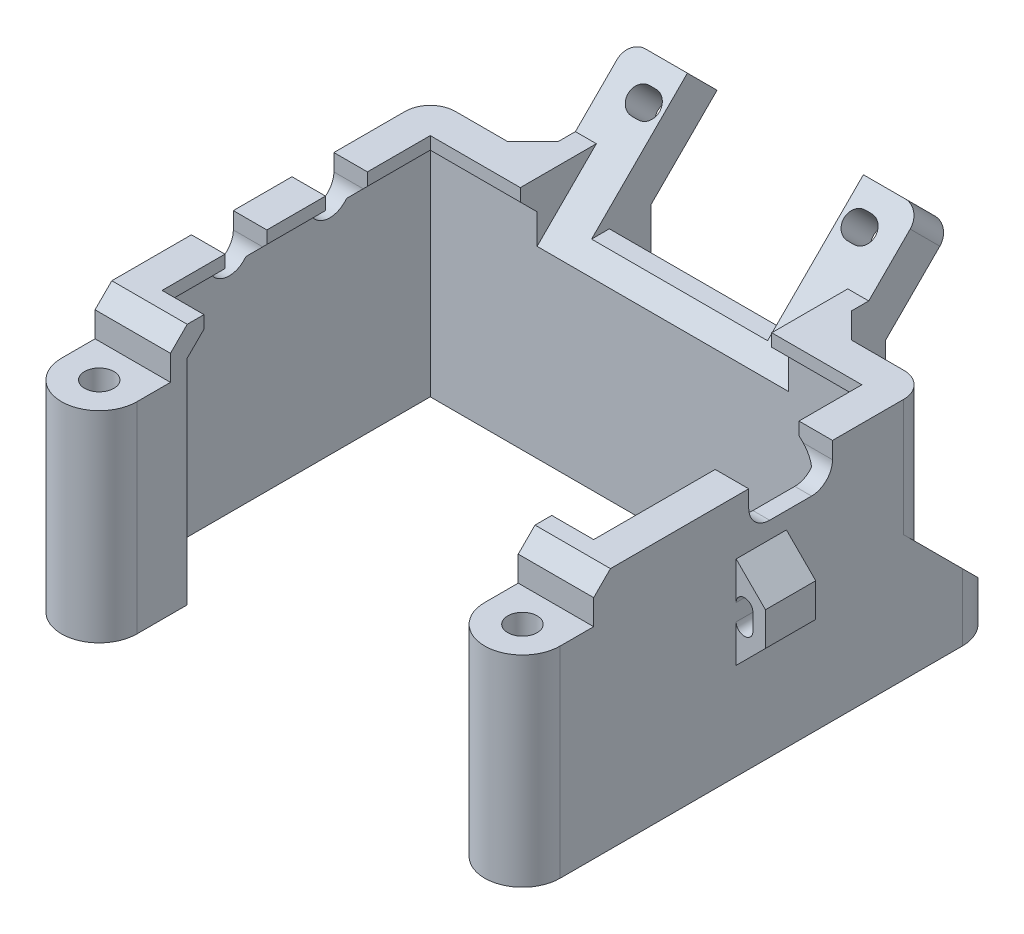
SolidWorks part; units mm, degrees
ref_plane "Front Plane" through (0, 0, 0) normal (0, 0, 1) x (1, 0, 0)
ref_plane "Top Plane" through (0, 0, 0) normal (0, 1, 0) x (1, 0, 0)
ref_plane "Right Plane" through (0, 0, 0) normal (1, 0, 0) x (0, 0, -1)
sketch "Sketch1" plane through (0, 0, 0) normal (0, 1, 0) x (1, 0, 0)
  line L0 (-29.75, 20) -> (29.75, 20)
  line L1 (-27.75, -18) -> (-20.75, -18)
  line L2 (-27.75, -18) -> (-27.75, 18)
  line L3 (-27.75, 18) -> (27.75, 18)
  line L4 (27.75, -18) -> (27.75, 18)
  line L5 (-27.75, -18) -> (27.75, 18) construction
  line L6 (-27.75, 18) -> (27.75, -18) construction
  line L7 (29.75, -20) -> (29.75, 20)
  line L8 (-29.75, -20) -> (-20.75, -20)
  line L9 (-29.75, -20) -> (-29.75, 20)
  line L10 (-20.75, -18) -> (-20.75, -20)
  line L11 (20.75, -18) -> (20.75, -20)
  line L12 (20.75, -18) -> (27.75, -18)
  line L13 (-27.75, -18) -> (27.75, -18) construction
  line L14 (20.75, -20) -> (29.75, -20)
  line L15 (-29.75, -20) -> (29.75, -20) construction
  point P0 (0, 0)
  dimension "D1" = 55.5
  dimension "D2" = 36
  dimension "D4" = 9
  dimension "D3" = 2
extrude "Boss-Extrude1" add sketch "Sketch1" along normal blind 29
sketch "Sketch2" plane through (0, 0, 0) normal (1, 0, 0) x (0, 0, -1)
  line L0 (18, 0) -> (18, 21.9289)
  line L1 (18, 21.9289) -> (31.435, 35.364)
  line L2 (31.435, 35.364) -> (34.9706, 31.8284)
  line L3 (34.9706, 31.8284) -> (23, 19.8579)
  line L4 (18, 0) -> (23, 0)
  line L5 (23, 0) -> (23, 19.8579)
  dimension "D1" = 45
  dimension "D2" = 5
  dimension "D3" = 5
  dimension "D4" = 19
  dimension "D5" = 5
extrude "Boss-Extrude2" add sketch "Sketch2" against normal blind 7 from offset 10.5 offset against normal yes
mirror "Mirror1" about plane through (0, 0, 0) normal (1, 0, 0) of "Boss-Extrude2"
sketch "Sketch3" plane through (0, 0, 0) normal (1, 0, 0) x (0, 0, -1)
  line L0 (18, 21.9289) -> (18, 29)
  line L1 (18, 29) -> (25.0711, 29)
  line L2 (25.0711, 29) -> (18, 21.9289)
  line L3 (18, 29) -> (18, 0) construction
  line L4 (20, 29) -> (-20, 29) construction
  line L5 (31.435, 35.364) -> (20, 23.9289) construction
extrude "Cut-Extrude1" cut sketch "Sketch3" against normal mid plane 30
sketch "Sketch4" plane through (0, 1.9645, 1.9645) normal (0, 0.7071, 0.7071) x (1, 0, 0)
  line L0 (-12.5, 43.234) -> (12.5, 43.234) construction
  line L1 (0, 43.234) -> (0, 0) construction
  line L2 (-15, 28.234) -> (15, 28.234) construction
  line L3 (-12.5, 43.234) -> (-13.25, 43.234) construction
  line L4 (-12.5, 41.734) -> (-13.25, 41.734)
  line L5 (-12.5, 44.734) -> (-13.25, 44.734)
  line L6 (12.5, 43.234) -> (13.25, 43.234) construction
  line L7 (12.5, 44.734) -> (13.25, 44.734)
  line L8 (12.5, 41.734) -> (13.25, 41.734)
  arc A0 (-12.5, 41.734) -> (-12.5, 44.734) centre (-12.5, 43.234) ccw
  arc A1 (-13.25, 44.734) -> (-13.25, 41.734) centre (-13.25, 43.234) ccw
  arc A2 (12.5, 44.734) -> (12.5, 41.734) centre (12.5, 43.234) ccw
  arc A3 (13.25, 41.734) -> (13.25, 44.734) centre (13.25, 43.234) ccw
  point P2 (-12.875, 43.234)
  point P13 (12.875, 43.234)
  dimension "D2" = 3
  dimension "D1" = 15
  dimension "D3" = 25
  dimension "D4" = 0.75
extrude "Cut-Extrude2" cut sketch "Sketch4" against normal up to next
sketch "Sketch7" plane through (-17.5, 0, 0) normal (-1, 0, 0) x (0, 0, 1)
  line L0 (-25.0711, 29) -> (-20, 29)
  line L1 (-31.435, 35.364) -> (-20, 23.9289) construction
  line L2 (-20, 29) -> (-20, 23.9289)
  line L3 (-20, 23.9289) -> (-25.0711, 29)
extrude "Boss-Extrude4" add sketch "Sketch7" against normal blind 2.5
mirror "Mirror2" about plane through (0, 0, 0) normal (1, 0, 0) of "Boss-Extrude4"
sketch "Sketch6" plane through (0, 0, -20) normal (0, 0, -1) x (-1, 0, 0)
  line L4 (10.5, 0) -> (10.5, 23.9289)
  line L5 (10.5, 23.9289) -> (-10.5, 23.9289)
  line L6 (-10.5, 23.9289) -> (-10.5, 0)
  line L7 (-10.5, 0) -> (10.5, 0)
  line L8 (10.5, 0) -> (10.5, 23.9289)
  line L9 (10.5, 23.9289) -> (-10.5, 23.9289)
  line L10 (-10.5, 23.9289) -> (-10.5, 0)
  line L11 (-10.5, 0) -> (10.5, 0)
  dimension "D1" = 0
extrude "Boss-Extrude3" add sketch "Sketch6" along normal up to surface (3 mm away) up to face at (14, 9.9289, -23)
chamfer "Chamfer1" distance 3 angle 45 2 edges at (-17.5, 14.5, -20) (17.5, 14.5, -20)
fillet "Fillet3" radius 2 2 edges at (17.5, 33.5962, -33.2028) (-17.5, 33.5962, -33.2028)
sketch "Sketch8" plane through (0, 0, 0) normal (0, -1, 0) x (1, 0, 0)
  line L0 (-29.75, -20) -> (-20.75, -20)
  line L1 (-20.5, -20) -> (-29.75, -20) construction
  line L2 (-20.75, -20) -> (-20.75, -24)
  line L3 (-29.75, -20) -> (-29.75, -24)
  arc A0 (-20.75, -24) -> (-29.75, -24) centre (-25.25, -24) cw
  dimension "D1" = 9
  dimension "D2" = 24
extrude "Boss-Extrude5" add sketch "Sketch8" against normal blind 3
mirror "Mirror5" about plane through (0, 0, 0) normal (1, 0, 0) of "Boss-Extrude5"
sketch "Sketch11" plane through (0, 0, 0) normal (0, -1, 0) x (1, 0, 0)
  line L0 (-20.75, 20) -> (-29.75, 20)
  line L1 (-29.75, 20) -> (-29.75, 24)
  line L2 (-20.75, 20) -> (-20.75, 24)
  line L3 (-29.75, -20) -> (-29.75, -24) construction
  arc A0 (-29.75, 24) -> (-20.75, 24) centre (-25.25, 24) cw
extrude "Boss-Extrude6" add sketch "Sketch11" against normal blind 24
mirror "Mirror6" about plane through (0, 0, 0) normal (1, 0, 0) of "Boss-Extrude6"
chamfer "Chamfer4" distance 9 angle 45 2 edges at (-25.25, 3, -20) (25.25, 3, -20)
sketch "Sketch9" plane through (0, 0, 0) normal (0, -1, 0) x (1, 0, 0)
  circle A0 centre (-25.25, -24) radius 1.75
  arc A1 (-29.75, -24) -> (-20.75, -24) centre (-25.25, -24) ccw construction
  circle A2 centre (25.25, -24) radius 1.75
  circle A3 centre (25.25, 24) radius 1.75
  circle A4 centre (-25.25, 24) radius 1.75
  arc A5 (20.75, -24) -> (29.75, -24) centre (25.25, -24) ccw construction
  arc A8 (-20.75, 24) -> (-29.75, 24) centre (-25.25, 24) ccw construction
  arc A9 (29.75, 24) -> (20.75, 24) centre (25.25, 24) ccw construction
  dimension "D1" = 3.5
extrude "Cut-Extrude4" cut sketch "Sketch9" against normal through all
sketch "Sketch10" plane through (0, 0, 0) normal (0, -1, 0) x (1, 0, 0)
  circle A0 centre (-25.25, -24) radius 3
  circle A1 centre (-25.25, -24) radius 1.75 construction
  circle A4 centre (25.25, -24) radius 3
  circle A7 centre (25.25, -24) radius 1.75 construction
  dimension "D1" = 6
extrude "Cut-Extrude5" cut sketch "Sketch10" against normal through all from offset 3 offset against normal yes
sketch "Sketch12" plane through (0, 29, 0) normal (0, 1, 0) x (1, 0, 0)
  line L0 (-20.75, -18) -> (-27.75, -18) construction
  line L1 (-27.75, -18) -> (-27.75, 18) construction
  line L2 (-27.75, 18) -> (-15, 18) construction
  line L3 (15, 18) -> (27.75, 18) construction
  line L4 (27.75, 18) -> (27.75, -18) construction
  line L5 (27.75, -18) -> (20.75, -18) construction
  line L6 (-20.75, -18) -> (-27.75, -18)
  line L7 (-27.75, -18) -> (-27.75, 18)
  line L8 (-27.75, 18) -> (-15, 18)
  line L9 (15, 18) -> (27.75, 18)
  line L10 (27.75, 18) -> (27.75, -18)
  line L11 (27.75, -18) -> (20.75, -18)
  line L12 (-20.75, -16) -> (-25.75, -16)
  line L13 (-25.75, -16) -> (-25.75, 16)
  line L14 (-25.75, 16) -> (-15, 16)
  line L15 (15, 16) -> (25.75, 16)
  line L16 (25.75, 16) -> (25.75, -16)
  line L17 (25.75, -16) -> (20.75, -16)
  line L18 (-20.75, -18) -> (-20.75, -16)
  line L19 (-15, 16) -> (-15, 18)
  line L20 (15, 16) -> (15, 18)
  line L21 (20.75, -18) -> (20.75, -16)
  dimension "D1" = 2
extrude "Boss-Extrude7" add sketch "Sketch12" against normal blind 3.5
chamfer "Chamfer5" distance 2 angle 45 6 edges at (23.25, 25.5, 16) (25.75, 25.5, 0) (20.375, 25.5, -16) (-20.375, 25.5, -16) (-25.75, 25.5, 0) (-23.25, 25.5, 16)
fillet "Fillet4" radius 3 2 edges at (-29.75, 20.5, -20) (29.75, 20.5, -20)
sketch "Sketch13" plane through (-29.75, 0, 0) normal (-1, 0, 0) x (0, 0, 1)
  line L0 (-8.5, 29) -> (-3.5, 29)
  line L1 (-3.5, 29) -> (-3.5, 27)
  line L2 (-8.5, 29) -> (-8.5, 27)
  line L3 (-17, 29) -> (20, 29) construction
  line L4 (-18, 25.5) -> (-18, 0) construction
  line L5 (3.5, 27) -> (3.5, 29)
  line L6 (3.5, 29) -> (8.5, 29)
  line L7 (8.5, 29) -> (8.5, 27)
  arc A0 (-8.5, 27) -> (-3.5, 27) centre (-6, 27) ccw
  arc A1 (3.5, 27) -> (8.5, 27) centre (6, 27) ccw
  dimension "D1" = 5
  dimension "D2" = 12
  dimension "D3" = 2
  dimension "D4" = 12
extrude "Cut-Extrude6" cut sketch "Sketch13" against normal up to next
sketch "Sketch14" plane through (29.75, 0, 0) normal (1, 0, 0) x (0, 0, -1)
  line L0 (8.5, 27) -> (8.5, 29)
  line L1 (8.5, 29) -> (-1.5, 29)
  line L2 (-1.5, 29) -> (-1.5, 27)
  line L3 (1, 24.5) -> (6, 24.5)
  line L4 (-20, 29) -> (17, 29) construction
  line L5 (18, 25.5) -> (18, 0) construction
  line L6 (8.5, 29) -> (8.5, 27) construction
  arc A0 (-1.5, 27) -> (1, 24.5) centre (1, 27) ccw
  arc A1 (8.5, 27) -> (6, 24.5) centre (6, 27) cw
  arc A2 (3.5, 27) -> (8.5, 27) centre (6, 27) ccw construction
  dimension "D1" = 12
  dimension "D2" = 5
extrude "Cut-Extrude7" cut sketch "Sketch14" against normal up to next
sketch "Sketch15" plane through (0, 0, 0) normal (0, 0, 1) x (1, 0, 0)
  line L0 (-29.75, 22.5) -> (-29.75, 11.5)
  line L1 (-29.75, 11.5) -> (-33.25, 15)
  line L2 (-33.25, 15) -> (-33.25, 19)
  line L3 (-33.25, 19) -> (-29.75, 22.5)
  line L4 (-29.75, 29) -> (-29.75, 15) construction
  point P6 (-29.75, 17)
  dimension "D1" = 3.5
  dimension "D2" = 4
  dimension "D3" = 45
  dimension "D4" = 17
extrude "Boss-Extrude8" add sketch "Sketch15" along normal mid plane 6
sketch "Sketch16" plane through (0, 0, 0) normal (0, 0, 1) x (1, 0, 0)
  line L0 (-30.75, 18) -> (-30.75, 16) construction
  line L1 (-29.75, 18) -> (-29.75, 16)
  line L2 (-31.75, 18) -> (-31.75, 16)
  line L3 (-30.75, 17) -> (-29.75, 17) construction
  line L4 (-29.75, 11.5) -> (-29.75, 22.5) construction
  arc A0 (-29.75, 18) -> (-31.75, 18) centre (-30.75, 18) ccw
  arc A1 (-31.75, 16) -> (-29.75, 16) centre (-30.75, 16) ccw
  point P2 (-30.75, 17)
  point P11 (-29.75, 17)
  dimension "D2" = 4
  dimension "D1" = 2
extrude "Cut-Extrude8" cut sketch "Sketch16" against normal mid plane 6
mirror "Mirror7" about plane through (0, 0, 0) normal (1, 0, 0) of "Boss-Extrude8", "Cut-Extrude8"
sketch "Sketch17" plane through (0, 0, 0) normal (0, 1, 0) x (1, 0, 0)
  line L0 (-17.5, 23) -> (17.5, 23) construction
  line L1 (6, 23) -> (-6, 23)
  line L2 (6, 23) -> (6, 33)
  line L3 (6, 33) -> (-6, 33)
  line L4 (-6, 23) -> (-6, 33)
  point P4 (0, 23)
  point P5 (0, 23)
  dimension "D1" = 12
  dimension "D2" = 10
extrude "Boss-Extrude9" add sketch "Sketch17" along normal up to surface (23.9289 mm away) up to face at (0, 23.9289, -21.5)
sketch "Sketch18" plane through (0, 0, 0) normal (1, 0, 0) x (0, 0, -1)
  line L0 (23, 11.9289) -> (23, 23.9289)
  line L1 (23, 23.9289) -> (27.0711, 23.9289)
  line L2 (27.0711, 23.9289) -> (27.0711, 16)
  line L3 (27.0711, 16) -> (23, 11.9289)
  line L7 (23, 19.8579) -> (34.9706, 31.8284) construction
  dimension "D1" = 12
extrude "Boss-Extrude10" add sketch "Sketch18" along normal up to surface and the other way up to surface up to face at (17.5, 28.4444, -26.9296) other way up to face at (-17.5, 28.4444, -26.9296)
sketch "Sketch19" plane through (0, 1.9645, 1.9645) normal (0, 0.7071, 0.7071) x (1, 0, 0)
  line L0 (-10.5, 31.0624) -> (10.5, 31.0624) construction
  line L1 (-10.5, 32.5624) -> (10.5, 32.5624)
  line L2 (-10.5, 32.5624) -> (-10.5, 47.234)
  line L3 (-10.5, 47.234) -> (10.5, 47.234)
  line L4 (10.5, 32.5624) -> (10.5, 47.234)
  line L5 (-10.5, 47.234) -> (-10.5, 31.0624) construction
  line L6 (10.5, 47.234) -> (10.5, 31.0624) construction
  line L7 (-15.5, 47.234) -> (-10.5, 47.234) construction
  dimension "D1" = 1.5
extrude "Cut-Extrude9" cut sketch "Sketch19" against normal through all
chamfer "Chamfer6" distance 2 angle 45 2 edges at (-25.25, 29, 20) (25.25, 29, 20)
